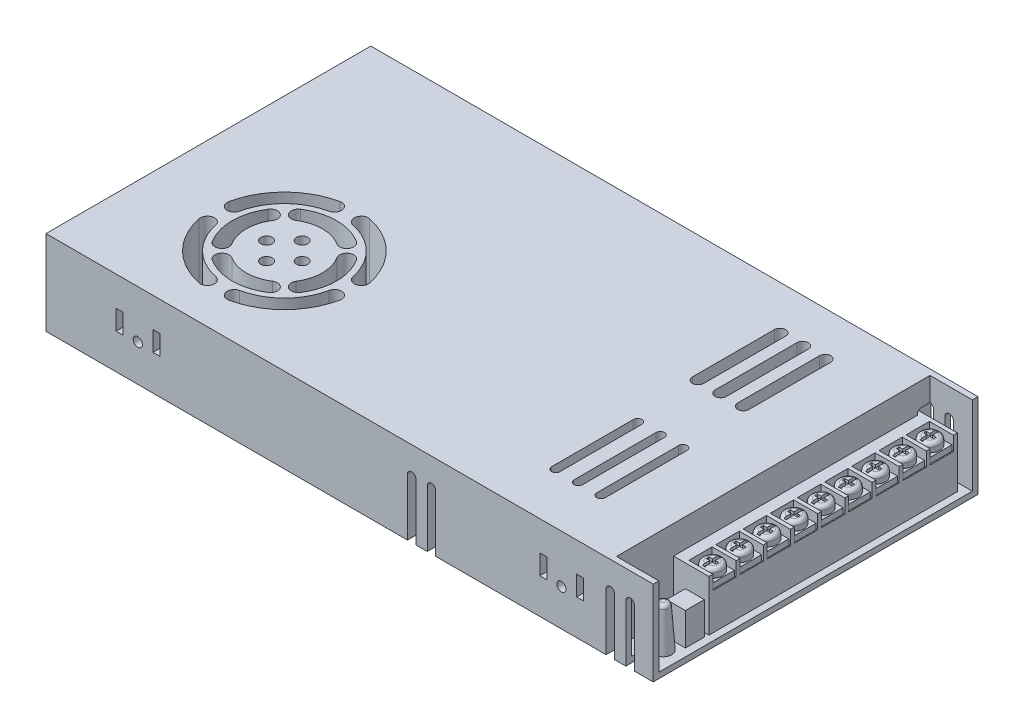
SolidWorks part; units mm, degrees
material "aluminio"
ref_plane "Alzado" through (0, 0, 0) normal (0, 0, 1) x (1, 0, 0)
ref_plane "Planta" through (0, 0, 0) normal (0, 1, 0) x (1, 0, 0)
ref_plane "Vista lateral" through (0, 0, 0) normal (1, 0, 0) x (0, 0, -1)
sketch "Croquis1" plane through (0, 0, 0) normal (0, 1, 0) x (1, 0, 0)
  line L1 (0, 0) -> (215, 0)
  line L2 (0, 0) -> (0, 115)
  line L3 (0, 115) -> (215, 115)
  line L4 (215, 0) -> (215, 115)
  dimension "D1" = 215
  dimension "D2" = 115
extrude "Saliente-Extruir1" add sketch "Croquis1" along normal blind 30
sketch "Croquis2" plane through (0, 30, 0) normal (0, 1, 0) x (1, 0, 0)
  line L0 (215, 0) -> (215, 115) construction
  line L1 (215, 113) -> (200, 113)
  line L2 (215, 113) -> (215, 2)
  line L3 (215, 2) -> (200, 2)
  line L4 (200, 113) -> (200, 2)
  line L5 (215, 115) -> (0, 115) construction
  line L6 (0, 115) -> (0, 0) construction
  line L7 (0, 0) -> (215, 0) construction
  dimension "D1" = 2
  dimension "D2" = 2
  dimension "D3" = 200
extrude "Cortar-Extruir1" cut sketch "Croquis2" against normal offset from surface (28 mm away) 2 up to face at (107.5, 0, -57.5)
sketch "Croquis7" plane through (0, 30, 0) normal (0, 1, 0) x (1, 0, 0)
  line L0 (176.4, 99.5) -> (176.4, 70.5) construction
  line L1 (178.4, 99.5) -> (178.4, 70.5)
  line L2 (174.4, 99.5) -> (174.4, 70.5)
  line L3 (200, 113) -> (200, 2) construction
  line L4 (178.5, 47) -> (178.5, 18) construction
  line L5 (180, 47) -> (180, 18)
  line L6 (177, 47) -> (177, 18)
  line L7 (0, 0) -> (215, 0) construction
  line L8 (215, 115) -> (0, 115) construction
  line L9 (168.4, 99.5) -> (168.4, 70.5) construction
  line L10 (170.4, 99.5) -> (170.4, 70.5)
  line L11 (166.4, 99.5) -> (166.4, 70.5)
  line L12 (170.5, 47) -> (170.5, 18) construction
  line L13 (172, 47) -> (172, 18)
  line L14 (169, 47) -> (169, 18)
  line L15 (160.4, 99.5) -> (160.4, 70.5) construction
  line L16 (162.4, 99.5) -> (162.4, 70.5)
  line L17 (158.4, 99.5) -> (158.4, 70.5)
  line L18 (162.5, 47) -> (162.5, 18) construction
  line L19 (164, 47) -> (164, 18)
  line L20 (161, 47) -> (161, 18)
  line L156 (154.5, 47) -> (154.5, 18) construction
  line L157 (156, 47) -> (156, 18)
  line L158 (153, 47) -> (153, 18)
  line L159 (144.4, 99.5) -> (144.4, 70.5) construction
  line L160 (146.4, 99.5) -> (146.4, 70.5)
  line L161 (142.4, 99.5) -> (142.4, 70.5)
  line L162 (146.5, 47) -> (146.5, 18) construction
  line L163 (148, 47) -> (148, 18)
  line L164 (145, 47) -> (145, 18)
  line L165 (152.4, 99.5) -> (152.4, 70.5) construction
  line L166 (154.4, 99.5) -> (154.4, 70.5)
  line L167 (150.4, 99.5) -> (150.4, 70.5)
  line L168 (154.5, 47) -> (154.5, 18) construction
  line L169 (156, 47) -> (156, 18)
  line L170 (153, 47) -> (153, 18)
  line L171 (144.4, 99.5) -> (144.4, 70.5) construction
  line L172 (146.4, 99.5) -> (146.4, 70.5)
  line L173 (142.4, 99.5) -> (142.4, 70.5)
  line L174 (146.5, 47) -> (146.5, 18) construction
  line L175 (148, 47) -> (148, 18)
  line L176 (145, 47) -> (145, 18)
  line L177 (152.4, 99.5) -> (152.4, 70.5) construction
  line L178 (154.4, 99.5) -> (154.4, 70.5)
  line L179 (150.4, 99.5) -> (150.4, 70.5)
  arc A0 (178.4, 99.5) -> (174.4, 99.5) centre (176.4, 99.5) ccw
  arc A1 (174.4, 70.5) -> (178.4, 70.5) centre (176.4, 70.5) ccw
  arc A2 (180, 47) -> (177, 47) centre (178.5, 47) ccw
  arc A3 (177, 18) -> (180, 18) centre (178.5, 18) ccw
  arc A4 (170.4, 99.5) -> (166.4, 99.5) centre (168.4, 99.5) ccw
  arc A5 (166.4, 70.5) -> (170.4, 70.5) centre (168.4, 70.5) ccw
  arc A6 (172, 47) -> (169, 47) centre (170.5, 47) ccw
  arc A7 (169, 18) -> (172, 18) centre (170.5, 18) ccw
  arc A8 (162.4, 99.5) -> (158.4, 99.5) centre (160.4, 99.5) ccw
  arc A9 (158.4, 70.5) -> (162.4, 70.5) centre (160.4, 70.5) ccw
  arc A10 (164, 47) -> (161, 47) centre (162.5, 47) ccw
  arc A11 (161, 18) -> (164, 18) centre (162.5, 18) ccw
  arc A110 (156, 47) -> (153, 47) centre (154.5, 47) ccw
  arc A111 (153, 18) -> (156, 18) centre (154.5, 18) ccw
  arc A112 (146.4, 99.5) -> (142.4, 99.5) centre (144.4, 99.5) ccw
  arc A113 (142.4, 70.5) -> (146.4, 70.5) centre (144.4, 70.5) ccw
  arc A114 (148, 47) -> (145, 47) centre (146.5, 47) ccw
  arc A115 (145, 18) -> (148, 18) centre (146.5, 18) ccw
  arc A116 (154.4, 99.5) -> (150.4, 99.5) centre (152.4, 99.5) ccw
  arc A117 (150.4, 70.5) -> (154.4, 70.5) centre (152.4, 70.5) ccw
  point P2 (176.4, 85)
  point P11 (178.5, 32.5)
  point P16 (178.5, 16.5)
  point P17 (176.4, 101.5)
  point P25 (168.4, 85)
  point P32 (170.5, 32.5)
  point P39 (160.4, 85)
  point P46 (162.5, 32.5)
  point P53 (154.5412, 34.5)
  point P60 (147.5412, 79.6)
  point P67 (147.5412, 34.5)
  point P80 (154.5412, 79.6)
  point P87 (154.5412, 34.5)
  point P94 (147.5412, 79.6)
  point P101 (147.5412, 34.5)
  point P108 (154.5412, 79.6)
  point P115 (154.5412, 34.5)
  point P122 (147.5412, 79.6)
  point P129 (147.5412, 34.5)
  point P136 (154.5412, 79.6)
  point P143 (154.5412, 34.5)
  point P150 (147.5412, 79.6)
  point P157 (147.5412, 34.5)
  point P164 (154.5412, 79.6)
  point P171 (157.5, 34.5)
  point P178 (150.5, 79.6)
  point P185 (150.5, 34.5)
  point P192 (157.5, 79.6)
  point P199 (157.5, 34.5)
  point P206 (150.5, 79.6)
  point P213 (150.5, 34.5)
  point P220 (157.5, 79.6)
  point P227 (157.5, 34.5)
  point P234 (150.5, 79.6)
  point P241 (150.5, 34.5)
  point P248 (157.5, 79.6)
  point P255 (157.5, 34.5)
  point P262 (150.5, 79.6)
  point P269 (150.5, 34.5)
  point P276 (157.5, 79.6)
  point P283 (157.5, 34.5)
  point P290 (150.5, 79.6)
  point P297 (150.5, 34.5)
  point P304 (157.5, 79.6)
  point P311 (157.5, 34.5)
  point P318 (150.5, 79.6)
  point P325 (150.5, 34.5)
  point P332 (157.5, 79.6)
  point P339 (154.5, 32.5)
  point P346 (144.4, 85)
  point P353 (146.5, 32.5)
  point P360 (152.4, 85)
  point P367 (154.5, 32.5)
  point P374 (144.4, 85)
  point P381 (146.5, 32.5)
  point P388 (152.4, 85)
  point P395 (154.5, 32.5)
  point P402 (144.4, 85)
  point P409 (146.5, 32.5)
  point P416 (152.4, 85)
  dimension "D1" = 21.6
  dimension "D2" = 16.5
  dimension "D5" = 20
  dimension "D6" = 1.5
  dimension "D3" = 13.5
  dimension "D4" = 20
  dimension "D8" = 4
  dimension "D9" = 33
  dimension "D7" = 5
sketch "Croquis5" plane through (0, 0, -115) normal (0, 0, -1) x (-1, 0, 0)
  line L0 (0, 30) -> (0, 0) construction
  line L2 (-215, 30) -> (-215, 0) construction
  line L3 (-215, 30) -> (0, 30) construction
  circle A0 centre (-182.5, 13) radius 1.625
  circle A1 centre (-32.5, 13) radius 1.625
  dimension "D1" = 3.25
  dimension "D2" = 3.25
  dimension "D4" = 17
  dimension "D5" = 17
  dimension "D3" = 32.5
  dimension "D6" = 32.5
extrude "Cortar-Extruir3" cut sketch "Croquis5" against normal through all
cosmetic thread "Rosca cosmética1" parameters "D2"=4
cosmetic thread "Rosca cosmética2" parameters "D2"=4
extrude "Cortar-Extruir5" cut sketch "Croquis7" against normal offset from surface (28 mm away) 2 up to face at (107.5, 0, -57.5)
sketch "Croquis10" plane through (0, 0, -115) normal (0, 0, -1) x (-1, 0, 0)
  line L0 (0, 30) -> (0, 0) construction
  line L1 (-24.85, 12.5) -> (-27.35, 12.5)
  line L2 (-24.85, 12.5) -> (-24.85, 19.5)
  line L3 (-24.85, 19.5) -> (-27.35, 19.5)
  line L4 (-27.35, 12.5) -> (-27.35, 19.5)
  line L5 (-37.85, 12.5) -> (-40.35, 12.5)
  line L6 (-37.85, 12.5) -> (-37.85, 19.5)
  line L7 (-37.85, 19.5) -> (-40.35, 19.5)
  line L8 (-40.35, 12.5) -> (-40.35, 19.5)
  line L9 (-215, 0) -> (0, 0) construction
  line L10 (-174.85, 12.5) -> (-177.35, 12.5)
  line L11 (-174.85, 12.5) -> (-174.85, 19.5)
  line L12 (-174.85, 19.5) -> (-177.35, 19.5)
  line L13 (-177.35, 12.5) -> (-177.35, 19.5)
  line L14 (-187.85, 12.5) -> (-190.35, 12.5)
  line L15 (-187.85, 12.5) -> (-187.85, 19.5)
  line L16 (-187.85, 19.5) -> (-190.35, 19.5)
  line L17 (-190.35, 12.5) -> (-190.35, 19.5)
  dimension "D1" = 2.5
  dimension "D2" = 2.5
  dimension "D3" = 7
  dimension "D4" = 7
  dimension "D5" = 10.5
  dimension "D6" = 24.85
  dimension "D7" = 12.5
  dimension "D8" = 12.5
  dimension "D10" = 134.5
  dimension "D11" = 12.5
  dimension "D9" = 2
extrude "Cortar-Extruir8 (no confirmat)" cut sketch "Croquis10" against normal through all
sketch "Croquis11" plane through (0, 0, 0) normal (0, 1, 0) x (1, 0, 0)
  line L0 (215, 2) -> (215, 113) construction
  line L1 (212.5, 110.2) -> (196.5, 110.2)
  line L2 (212.5, 110.2) -> (212.5, 22.2)
  line L3 (212.5, 22.2) -> (196.5, 22.2)
  line L4 (196.5, 110.2) -> (196.5, 22.2)
  line L5 (215, 113) -> (200, 113) construction
  line L6 (200, 2) -> (215, 2) construction
  dimension "D1" = 20.2
  dimension "D2" = 16
  dimension "D3" = 2.5
  dimension "D4" = 2.8
extrude "Saliente-Extruir2" add sketch "Croquis11" along normal blind 20 separate body
sketch "Croquis12" plane through (212.5, 0, 0) normal (1, 0, 0) x (0, 0, -1)
  line L0 (22.2, 20) -> (110.2, 20) construction
  line L1 (23.6, 20) -> (31.8667, 20)
  line L2 (23.6, 20) -> (23.6, 15)
  line L3 (23.6, 15) -> (31.8667, 15)
  line L4 (31.8667, 20) -> (31.8667, 15)
  line L6 (41.4833, 20) -> (41.4833, 15)
  line L7 (33.2167, 15) -> (41.4833, 15)
  line L8 (33.2167, 20) -> (33.2167, 15)
  line L9 (33.2167, 20) -> (41.4833, 20)
  line L10 (51.1, 20) -> (51.1, 15)
  line L11 (42.8333, 15) -> (51.1, 15)
  line L12 (42.8333, 20) -> (42.8333, 15)
  line L13 (42.8333, 20) -> (51.1, 20)
  line L14 (60.7167, 20) -> (60.7167, 15)
  line L15 (52.45, 15) -> (60.7167, 15)
  line L16 (52.45, 20) -> (52.45, 15)
  line L17 (52.45, 20) -> (60.7167, 20)
  line L18 (70.3333, 20) -> (70.3333, 15)
  line L19 (62.0667, 15) -> (70.3333, 15)
  line L20 (62.0667, 20) -> (62.0667, 15)
  line L21 (62.0667, 20) -> (70.3333, 20)
  line L22 (79.95, 20) -> (79.95, 15)
  line L23 (71.6833, 15) -> (79.95, 15)
  line L24 (71.6833, 20) -> (71.6833, 15)
  line L25 (71.6833, 20) -> (79.95, 20)
  line L26 (89.5667, 20) -> (89.5667, 15)
  line L27 (81.3, 15) -> (89.5667, 15)
  line L28 (81.3, 20) -> (81.3, 15)
  line L29 (81.3, 20) -> (89.5667, 20)
  line L30 (99.1833, 20) -> (99.1833, 15)
  line L31 (90.9167, 15) -> (99.1833, 15)
  line L32 (90.9167, 20) -> (90.9167, 15)
  line L33 (90.9167, 20) -> (99.1833, 20)
  line L34 (108.8, 20) -> (108.8, 15)
  line L35 (100.5333, 15) -> (108.8, 15)
  line L36 (100.5333, 20) -> (100.5333, 15)
  line L37 (100.5333, 20) -> (108.8, 20)
  line L39 (110.2, 20) -> (110.2, 0) construction
  line L40 (22.2, 20) -> (22.2, 0) construction
  dimension "D1" = 1.4
  dimension "D2" = 5
  dimension "D3" = 1.4
  dimension "D5" = 1.35
  dimension "D4" = 9
extrude "Cortar-Extruir11" cut sketch "Croquis12" against normal blind 8.5
sketch "Croquis17" plane through (0, 0, -115) normal (0, 0, -1) x (-1, 0, 0)
  line L0 (-136.5, 20.2) -> (-136.5, 0) construction
  line L1 (-135, 20.2) -> (-135, 0)
  line L2 (-138, 20.2) -> (-138, 0)
  line L3 (-215, 0) -> (0, 0) construction
  line L4 (-129.5, 20.2) -> (-129.5, 0) construction
  line L5 (-215, 30) -> (-215, 0) construction
  line L6 (-128, 20.2) -> (-128, 0)
  line L7 (-131, 20.2) -> (-131, 0)
  line L8 (-199.8, 0) -> (-199.8, 20.2) construction
  line L9 (-201.3, 0) -> (-201.3, 20.2)
  line L10 (-198.3, 0) -> (-198.3, 20.2)
  line L11 (-206.8, 0) -> (-206.8, 20.2) construction
  line L12 (-208.3, 0) -> (-208.3, 20.2)
  line L13 (-205.3, 0) -> (-205.3, 20.2)
  arc A0 (-135, 20.2) -> (-138, 20.2) centre (-136.5, 20.2) ccw
  arc A1 (-138, 0) -> (-135, 0) centre (-136.5, 0) ccw
  arc A2 (-128, 20.2) -> (-131, 20.2) centre (-129.5, 20.2) ccw
  arc A3 (-131, 0) -> (-128, 0) centre (-129.5, 0) ccw
  arc A4 (-201.3, 0) -> (-198.3, 0) centre (-199.8, 0) ccw
  arc A5 (-198.3, 20.2) -> (-201.3, 20.2) centre (-199.8, 20.2) ccw
  arc A6 (-208.3, 0) -> (-205.3, 0) centre (-206.8, 0) ccw
  arc A7 (-205.3, 20.2) -> (-208.3, 20.2) centre (-206.8, 20.2) ccw
  point P2 (-136.5, 10.1)
  point P7 (-136.5, 21.7)
  point P8 (-136.5, -1.5)
  point P16 (-129.5, 10.1)
  point P21 (-129.5, 21.7)
  point P22 (-129.5, -1.5)
  point P24 (-199.8, 10.1)
  point P31 (-206.8, 10.1)
  dimension "D2" = 1.5
  dimension "D1" = 21.7
  dimension "D3" = 2
  dimension "D4" = 77
  dimension "D6" = 6.7
  dimension "D5" = 4
  dimension "D7" = 4
extrude "Cortar-Extruir15" cut sketch "Croquis17" against normal blind 6.4
extrude "Cut-Extrude2" cut sketch "Croquis17<2>" against normal blind 10 from offset 110 offset against normal yes
sketch "Croquis17<2>" plane through (0, 0, -115) normal (0, 0, -1) x (-1, 0, 0) same geometry as "Croquis17"
fillet "Redondeo3" radius 1.3 22 edges at (128, 10.1, -108.6) (129.5, 21.7, -108.6) (136.5, 21.7, -108.6) (198.8126, 21.3292, -108.6) (131, 10.1, -108.6) (135, 10.1, -108.6) (138, 10.1, -108.6) (198.3, 10.1, -108.6) (201.3, 1, -108.6) (205.3, 1, -108.6) (208.3, 1, -108.6) (198.8126, 21.3292, -5) (128, 10.1, -5) (129.5, 21.7, -5) (135, 10.1, -5) (136.5, 21.7, -5) (205.3, 1, -5) (198.3, 10.1, -5) (208.3, 1, -5) (201.3, 1, -5) (131, 10.1, -5) (138, 10.1, -5)
sketch "Croquis18" plane through (0, 30, 0) normal (0, 1, 0) x (1, 0, 0)
  line L0 (33.9854, 45.4648) -> (33.9854, 28.3352) construction
  line L1 (70.0042, 41.65) -> (70.0042, 32.15) construction
  line L2 (0, 115) -> (0, 0) construction
  line L3 (0, 0) -> (215, 0) construction
  arc A0 (42.2337, 61.8503) -> (22.5497, 42.1663) centre (47.5, 36.9) ccw
  arc A1 (43.2663, 56.9581) -> (27.4419, 41.1337) centre (47.5, 36.9) ccw
  arc A2 (22.5497, 42.1663) -> (27.4419, 41.1337) centre (24.9958, 41.65) ccw
  arc A3 (43.2663, 56.9581) -> (42.2337, 61.8503) centre (42.75, 59.4042) ccw
  arc A4 (67.5581, 41.1337) -> (51.7337, 56.9581) centre (47.5, 36.9) ccw
  arc A5 (52.7663, 61.8503) -> (51.7337, 56.9581) centre (52.25, 59.4042) ccw
  arc A6 (72.4503, 42.1663) -> (52.7663, 61.8503) centre (47.5, 36.9) ccw
  arc A7 (67.5581, 41.1337) -> (72.4503, 42.1663) centre (70.0042, 41.65) ccw
  arc A8 (51.7337, 16.8419) -> (67.5581, 32.6663) centre (47.5, 36.9) ccw
  arc A9 (72.4503, 31.6337) -> (67.5581, 32.6663) centre (70.0042, 32.15) ccw
  arc A10 (52.7663, 11.9497) -> (72.4503, 31.6337) centre (47.5, 36.9) ccw
  arc A11 (51.7337, 16.8419) -> (52.7663, 11.9497) centre (52.25, 14.3958) ccw
  arc A12 (27.4419, 32.6663) -> (43.2663, 16.8419) centre (47.5, 36.9) ccw
  arc A13 (42.2337, 11.9497) -> (43.2663, 16.8419) centre (42.75, 14.3958) ccw
  arc A14 (22.5497, 31.6337) -> (42.2337, 11.9497) centre (47.5, 36.9) ccw
  arc A15 (27.4419, 32.6663) -> (22.5497, 31.6337) centre (24.9958, 32.15) ccw
  arc A16 (33.9854, 28.3352) -> (33.9854, 45.4648) centre (47.5, 36.9) cw construction
  arc A17 (31.8738, 46.8031) -> (31.8738, 26.9969) centre (47.5, 36.9) ccw
  arc A18 (36.0971, 44.1266) -> (36.0971, 29.6734) centre (47.5, 36.9) ccw
  arc A19 (36.0971, 44.1266) -> (31.8738, 46.8031) centre (33.9854, 45.4648) ccw
  arc A20 (31.8738, 26.9969) -> (36.0971, 29.6734) centre (33.9854, 28.3352) ccw
  arc A21 (38.9352, 50.4146) -> (56.0648, 50.4146) centre (47.5, 36.9) cw construction
  arc A22 (57.4031, 52.5262) -> (37.5969, 52.5262) centre (47.5, 36.9) ccw
  arc A23 (54.7266, 48.3029) -> (40.2734, 48.3029) centre (47.5, 36.9) ccw
  arc A24 (54.7266, 48.3029) -> (57.4031, 52.5262) centre (56.0648, 50.4146) ccw
  arc A25 (37.5969, 52.5262) -> (40.2734, 48.3029) centre (38.9352, 50.4146) ccw
  arc A26 (61.0146, 45.4648) -> (61.0146, 28.3352) centre (47.5, 36.9) cw construction
  arc A27 (63.1262, 26.9969) -> (63.1262, 46.8031) centre (47.5, 36.9) ccw
  arc A28 (58.9029, 29.6734) -> (58.9029, 44.1266) centre (47.5, 36.9) ccw
  arc A29 (58.9029, 29.6734) -> (63.1262, 26.9969) centre (61.0146, 28.3352) ccw
  arc A30 (63.1262, 46.8031) -> (58.9029, 44.1266) centre (61.0146, 45.4648) ccw
  arc A31 (38.9352, 23.3854) -> (56.0648, 23.3854) centre (47.5, 36.9) ccw construction
  arc A32 (37.5969, 21.2738) -> (57.4031, 21.2738) centre (47.5, 36.9) ccw
  arc A33 (40.2734, 25.4971) -> (54.7266, 25.4971) centre (47.5, 36.9) ccw
  arc A34 (40.2734, 25.4971) -> (37.5969, 21.2738) centre (38.9352, 23.3854) ccw
  arc A35 (57.4031, 21.2738) -> (54.7266, 25.4971) centre (56.0648, 23.3854) ccw
  circle A36 centre (47.5, 36.9) radius 6.3 construction
  circle A37 centre (41.2, 36.9) radius 2
  circle A38 centre (47.5, 43.2) radius 2
  circle A39 centre (53.8, 36.9) radius 2
  circle A40 centre (47.5, 30.6) radius 2
  point P2 (24.6901, 48.3)
  point P33 (31.5, 36.9)
  point P42 (47.5, 52.9)
  point P45 (47.5, 36.9)
  point P48 (63.5, 36.9)
  point P56 (47.5, 20.9)
  dimension "D1" = 51
  dimension "D2" = 41
  dimension "D5" = 5
  dimension "D6" = 4.5
  dimension "D7" = 5
  dimension "D8" = 6.65
  dimension "D10" = 5
  dimension "D11" = 37
  dimension "D12" = 2
  dimension "D13" = 4
  dimension "D14" = 16.6
  dimension "D3" = 47.5
  dimension "D4" = 36.9
  dimension "D9" = 4
extrude "Cortar-Extruir17" cut sketch "Croquis18" against normal offset from surface (28 mm away) 2 up to face at (163.4846, 0, -57.0692)
sketch "Croquis28" plane through (0, 0, 0) normal (0, -1, 0) x (1, 0, 0)
  line L2 (208.3, 0) -> (215, 0) construction
  line L3 (215, 0) -> (215, -115) construction
  line L7 (32.5, -32.5) -> (182.5, -32.5) construction
  line L8 (32.5, -32.5) -> (32.5, -82.5) construction
  line L9 (32.5, -82.5) -> (182.5, -82.5) construction
  line L10 (182.5, -32.5) -> (182.5, -82.5) construction
  circle A0 centre (32.5, -32.5) radius 1.625
  circle A1 centre (32.5, -82.5) radius 1.625
  circle A2 centre (182.5, -32.5) radius 1.625
  circle A3 centre (182.5, -82.5) radius 1.625
  dimension "D1" = 3.25
  dimension "D2" = 32.5
  dimension "D3" = 150
  dimension "D4" = 50
  dimension "D6" = 32.5
extrude "Cortar-Extruir23" cut sketch "Croquis28" against normal blind 2
cosmetic thread "Rosca cosmética3" parameters "D2"=4
cosmetic thread "Rosca cosmética4" parameters "D2"=4
cosmetic thread "Rosca cosmética5" parameters "D2"=4
cosmetic thread "Rosca cosmética6" parameters "D2"=4
sketch "Sketch1" plane through (0, 30, 0) normal (0, 1, 0) x (1, 0, 0)
  line L0 (187.9485, 115) -> (187.9485, 1.484) construction
  line L3 (215, 115) -> (0, 115) construction
  text T0 "<b>   |POWER AC|       POWER DC      |</b>" font "Century Gothic" height in points 16
extrude "Cut-Extrude3" [suppressed] cut sketch "Sketch1" against normal blind 1
sketch "Croquis29" plane through (0, 15, 0) normal (0, 1, 0) x (1, 0, 0)
  line L0 (204, 23.6) -> (212.5, 31.8667) construction
  circle A0 centre (208.25, 27.7333) radius 3.5
  dimension "D1" = 7
extrude "Saliente-Extruir3" add sketch "Croquis29" along normal blind 5 separate body
fillet "Redondeo4" radius 1.3 1 edges at (208.25, 20, -24.2333)
sketch "Croquis30" plane through (0, 20, 0) normal (0, 1, 0) x (1, 0, 0)
  line L0 (206.05, 27.7333) -> (210.45, 27.7333) construction
  line L1 (207.75, 30.7333) -> (208.75, 30.7333)
  line L2 (207.75, 30.7333) -> (207.75, 24.7333)
  line L3 (207.75, 24.7333) -> (208.75, 24.7333)
  line L4 (208.75, 30.7333) -> (208.75, 24.7333)
  line L5 (208.25, 30.7333) -> (208.25, 24.7333) construction
  circle A0 centre (208.25, 27.7333) radius 2.2 construction
  point P11 (208.25, 27.7333)
  dimension "D1" = 6
  dimension "D2" = 1
extrude "Cortar-Extruir24" cut sketch "Croquis30" against normal blind 1
sketch "Croquis31" plane through (0, 20, 0) normal (0, 1, 0) x (1, 0, 0)
  line L0 (208.25, 30.7333) -> (208.25, 24.7333) construction
  line L1 (206.5, 28.2333) -> (210, 28.2333)
  line L2 (206.5, 28.2333) -> (206.5, 27.2333)
  line L3 (206.5, 27.2333) -> (210, 27.2333)
  line L4 (210, 28.2333) -> (210, 27.2333)
  line L5 (208.75, 24.7333) -> (207.75, 24.7333) construction
  line L6 (207.75, 30.7333) -> (208.75, 30.7333) construction
  line L7 (206.5, 27.7333) -> (210, 27.7333) construction
  point P12 (208.25, 27.7333)
  dimension "D1" = 3.5
extrude "Cortar-Extruir25" cut sketch "Croquis31" against normal up to surface (1 mm away) up to face at (208.25, 19, -27.7333)
sketch "Croquis32" plane through (0, 15, 0) normal (0, 1, 0) x (1, 0, 0)
  line L0 (204.35, 23.8333) -> (212.15, 31.6333) construction
  line L1 (204.35, 31.6333) -> (212.15, 31.6333)
  line L2 (204.35, 31.6333) -> (204.35, 23.8333)
  line L3 (204.35, 23.8333) -> (212.15, 23.8333)
  line L4 (212.15, 31.6333) -> (212.15, 23.8333)
  arc A0 (208.75, 25.5909) -> (208.75, 29.8758) centre (208.25, 27.7333) ccw construction
  point P4 (208.25, 27.7333)
  dimension "D1" = 7.8
extrude "Saliente-Extruir4" add sketch "Croquis32" along normal blind 2
sketch "Croquis33" plane through (0, 15, 0) normal (0, 1, 0) x (1, 0, 0)
  line L0 (204, 46.9667) -> (204, 56.5833) construction
  line L1 (204, 42.8333) -> (204, 51.1) construction
  line L2 (204, 52.45) -> (204, 60.7167) construction
  dimension "D1" = 9.6167
pattern_linear "MatrizL1" count 9 spacing 9.62 along (0, 0, -1) of bodies 132
sketch "Croquis34" plane through (0, 2, 0) normal (0, 1, 0) x (1, 0, 0)
  line L0 (215, 2) -> (215, 113) construction
  line L1 (205.6, 14.1) -> (212.3, 14.1)
  line L2 (205.6, 14.1) -> (205.6, 20.8)
  line L3 (205.6, 20.8) -> (212.3, 20.8)
  line L4 (212.3, 14.1) -> (212.3, 20.8)
  line L5 (196.5, 22.2) -> (212.5, 22.2) construction
  dimension "D1" = 6.7
  dimension "D2" = 2.7
  dimension "D3" = 1.4
extrude "Saliente-Extruir5" add sketch "Croquis34" along normal blind 11.5 separate body
sketch "Croquis35" plane through (0, 2, 0) normal (0, 1, 0) x (1, 0, 0)
  line L0 (208.95, 9.6) -> (208.95, 14.1) construction
  line L1 (205.6, 14.1) -> (212.3, 14.1) construction
  circle A0 centre (208.95, 9.6) radius 3
  dimension "D2" = 6
  dimension "D1" = 4.5
extrude "Saliente-Extruir6" add sketch "Croquis35" along normal blind 15 draft 4 separate body
fillet "Redondeo5" radius 1.3 1 edges at (208.95, 17, -7.6489)
